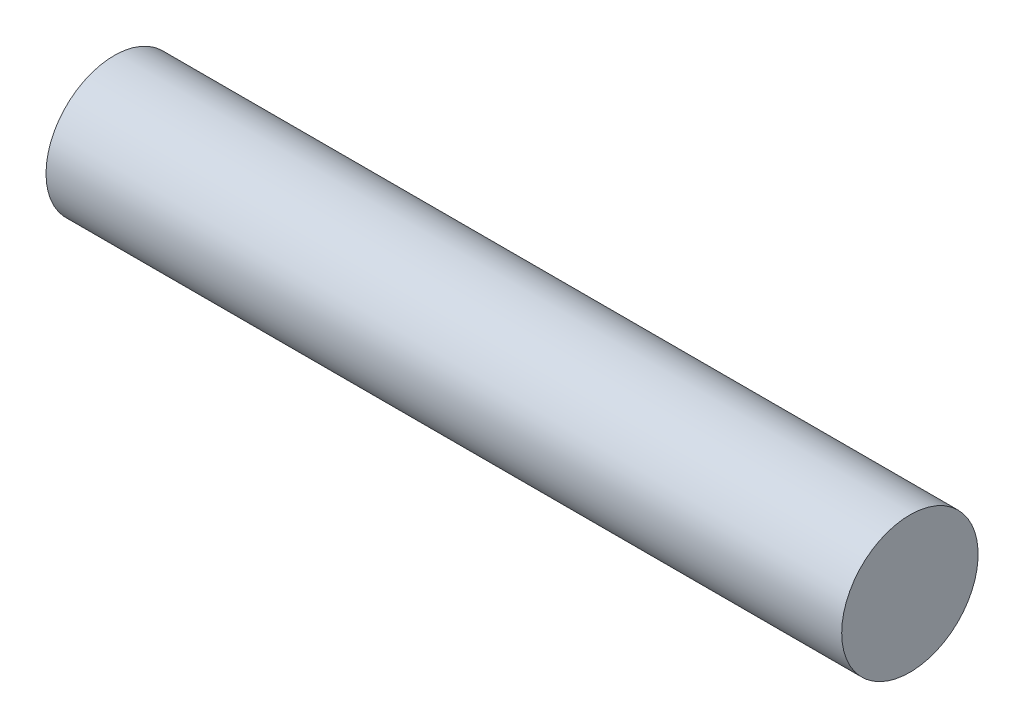
SolidWorks part; units mm, degrees
material "Alloy Steel"
ref_plane "Front Plane" through (0, 0, 0) normal (0, 0, 1) x (1, 0, 0)
ref_plane "Top Plane" through (0, 0, 0) normal (0, 1, 0) x (1, 0, 0)
ref_plane "Right Plane" through (0, 0, 0) normal (1, 0, 0) x (0, 0, -1)
sketch "Sketch1" plane through (0, 0, 0) normal (0, 0, 1) x (1, 0, 0)
  line L0 (0, 0) -> (34.9915, 0) construction
  line L1 (0, 0) -> (0, 3)
  line L2 (0, 3) -> (34.9915, 3)
  line L7 (34.9915, 3) -> (34.9915, 0)
  line L8 (0, 0) -> (34.9915, 0)
  dimension "D1" = 34.9915
  dimension "D4" = 6
revolve "Revolve1" add sketch "Sketch1" angle 360 about L0
